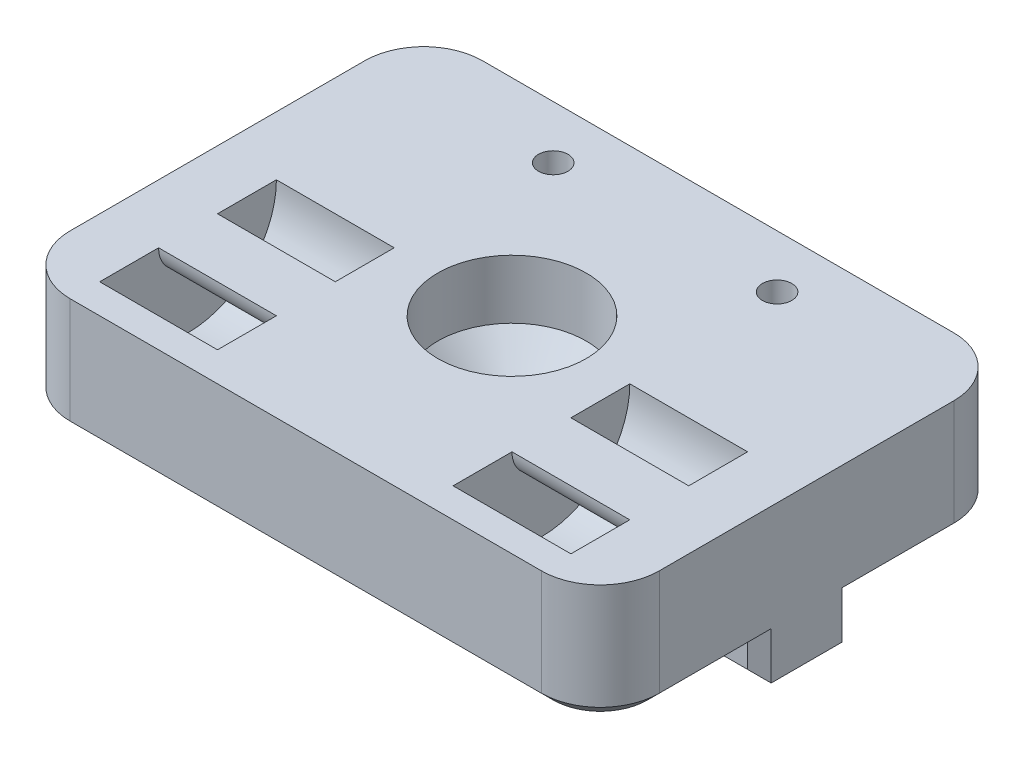
SolidWorks part; units mm, degrees
material "ABS"
ref_plane "Front Plane" through (0, 0, 0) normal (0, 0, 1) x (1, 0, 0)
ref_plane "Top Plane" through (0, 0, 0) normal (0, 1, 0) x (1, 0, 0)
ref_plane "Right Plane" through (0, 0, 0) normal (1, 0, 0) x (0, 0, -1)
sketch "Sketch1" plane through (0, 0, 0) normal (1, 0, 0) x (0, 0, -1)
  line L0 (-17.5, 10) -> (17.5, 10)
  line L1 (17.5, 10) -> (17.5, 0)
  line L2 (17.5, 0) -> (4, 0)
  line L3 (4, 0) -> (4, -3)
  line L4 (4, -3) -> (-4, -3)
  line L5 (-4, -3) -> (-4, 0)
  line L6 (-4, 0) -> (-17.5, 0)
  line L7 (-17.5, 0) -> (-17.5, 10)
  dimension "D1" = 17.5
  dimension "D2" = 17.5
  dimension "D3" = 8
  dimension "D4" = 3
  dimension "D5" = 10
extrude "Boss-Extrude1" add sketch "Sketch1" along normal mid plane 50
hole_wizard "CSK for M6 Flat Head Machine Screw1" positions "Sketch2" profile "Sketch3" countersink size "M6" standard "ANSI Metric" end condition up to next
sketch "Sketch2" plane through (0, 10, 0) normal (0, 1, 0) x (1, 0, 0)
  point P0 (0, 0)
sketch "Sketch3" plane through (0, 10, 0) normal (1, 0, 0) x (0, 0, 1)
  line L0 (0, 0) -> (0, 13)
  line L1 (0, 13) -> (3.3, 13)
  line L2 (3.3, 13) -> (3.3, 8)
  line L3 (3.3, 8) -> (6.3, 5)
  line L4 (6.3, 5) -> (6.3, 0)
  line L6 (6.3, 0) -> (0, 0)
  line L7 (-3.3, 8) -> (-6.3, 5) construction
  line L11 (0, -6.35) -> (0, 107.95) construction
  dimension "Thru Hole Dia." = 6.6
  dimension "Thru Hole Depth" = 13
  dimension "C'Sink Dia." = 12.6
  dimension "C'Sink Angle" = 90
  dimension "Head Clearance" = 5
ref_plane "Plane1" through (15, 0, 0) normal (1, 0, 0) x (0, 0, -1)
sketch "Sketch4" plane through (15, 0, 0) normal (1, 0, 0) x (0, 0, -1)
  line L0 (-15, 10) -> (-10, 10)
  line L1 (17.5, 10) -> (-17.5, 10) construction
  line L2 (-5, 10) -> (0, 10)
  arc A0 (-10, 10) -> (-5, 10) centre (-7.5, 10) ccw
  arc A1 (-15, 10) -> (0, 10) centre (-7.5, 10) ccw
  point P8 (-12.5, 10)
  dimension "D1" = 5
  dimension "D2" = 7.5
  dimension "D3" = 5
extrude "Cut-Extrude1" cut sketch "Sketch4" against normal mid plane 10
mirror "Mirror1" about plane through (0, 0, 0) normal (1, 0, 0) of "Cut-Extrude1"
fillet "Fillet1" radius 5 4 edges at (25, 5, 17.5) (25, 5, -17.5) (-25, 5, 17.5) (-25, 5, -17.5)
chamfer "Chamfer1" distance 1 angle 45 16 edges at (0, 0, 17.5) (0, 0, -17.5) (0, -3, 4) (0, -3, -4) (25, 0, 8.25) (-25, 0, 8.25) (23.5355, 0, 16.0355) (-23.5355, 0, 16.0355) (25, 0, -8.25) (-25, 0, -8.25) (23.5355, 0, -16.0355) (-23.5355, 0, -16.0355) (25, -1.5, 4) (-25, -1.5, 4) (25, -1.5, -4) (-25, -1.5, -4)
hole_wizard "M3x0.5 Tapped Hole1" positions "Sketch5" profile "Sketch6" tap size "M3x0.5" standard "ANSI Metric" end condition up to next
sketch "Sketch5" plane through (0, 10, 0) normal (0, 1, 0) x (1, 0, 0)
  line L0 (-9.5, 13) -> (9.5, 13)
  line L2 (0, -7.15) -> (0, 7.15) construction
  point P0 (-9.5, 13)
  point P2 (9.5, 13)
  point P10 (0, 13)
  dimension "D1" = 19
  dimension "D2" = 13
sketch "Sketch6" plane through (-9.5, 10, -13) normal (1, 0, 0) x (0, 0, 1)
  line L0 (0, 0) -> (0, 10)
  line L1 (0, 10) -> (1.25, 10)
  line L2 (1.25, 10) -> (1.25, 0)
  line L5 (1.25, 0) -> (0, 0)
  line L11 (0, -6.35) -> (0, 107.95) construction
  dimension "Thru Tap Drill Dia." = 2.5
  dimension "Thru Tap Drill Depth" = 10
cosmetic thread "Hole Thread1" parameters "D2"=3
cosmetic thread "Hole Thread2" parameters "D2"=3
